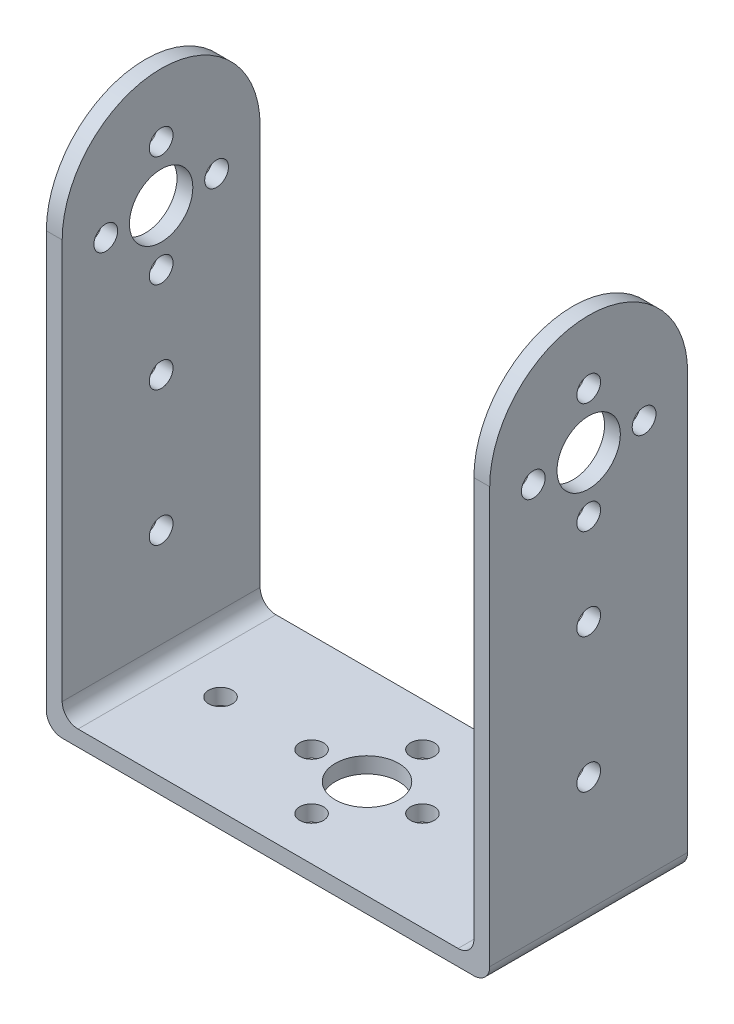
SolidWorks part; units mm, degrees
ref_plane "Front Plane" through (0, 0, 0) normal (0, 0, 1) x (1, 0, 0)
ref_plane "Top Plane" through (0, 0, 0) normal (0, 1, 0) x (1, 0, 0)
ref_plane "Right Plane" through (0, 0, 0) normal (1, 0, 0) x (0, 0, -1)
sketch "Sketch1" plane through (0, 0, 0) normal (0, 1, 0) x (1, 0, 0)
  line L0 (-26, 12.5) -> (-28, 12.5)
  line L2 (-26, -12.5) -> (-26, 12.5)
  line L4 (26, -12.5) -> (26, 12.5)
  line L5 (-26, -12.5) -> (-28, -12.5)
  line L6 (-26, 12.5) -> (26, 12.5)
  line L7 (28, -12.5) -> (26, -12.5)
  line L8 (28, -12.5) -> (28, 12.5)
  line L9 (28, 12.5) -> (26, 12.5)
  line L10 (-28, -12.5) -> (-28, 12.5)
  line L11 (-26, -12.5) -> (26, -12.5)
  line L12 (-26, 12.5) -> (26, -12.5) construction
  line L13 (26, 12.5) -> (-26, -12.5) construction
  point P0 (0, 0)
  point P6 (0, 0)
  point P11 (0, 0)
  dimension "D1" = 2
  dimension "D2" = 2
  dimension "D3" = 25
  dimension "D4" = 52
extrude "Boss-Extrude1" add sketch "Sketch1" against normal blind 2 contours L2 L11 L4 L6 | L10 L5 L2 L0 | L8 L9 L4 L7 region at (-27, 0, 0) region at (0, 0, 0) region at (27, 0, 0)
extrude "Boss-Extrude2" add sketch "Sketch1<3>" along normal blind 65 contours L10 L5 L2 L0 | L8 L9 L4 L7 region at (-27, 0, 0) region at (27, 0, 0)
sketch "Sketch1<3>" plane through (0, 0, 0) normal (0, 1, 0) x (1, 0, 0) same geometry as "Sketch1"
fillet "Fillet4" radius 2 4 edges at (28, -2, 0) (26, 0, 0) (-28, -2, 0) (-26, 0, 0)
sketch "Sketch2" plane through (28, 0, 0) normal (1, 0, 0) x (0, 0, -1)
  line L0 (-12.5, 0) -> (-12.5, 65) construction
  line L1 (12.5, 0) -> (12.5, 65) construction
  line L2 (-12.5, 65) -> (12.5, 65) construction
  line L4 (-12.5, 52.5) -> (-12.5, 65)
  line L5 (-12.5, 65) -> (0, 65)
  line L6 (0, 65) -> (12.5, 65)
  line L7 (12.5, 65) -> (12.5, 52.5)
  line L8 (0, -2) -> (0, 14.5) construction
  line L9 (12.5, -2) -> (-12.5, -2) construction
  line L10 (0, 14.5) -> (0, 31.5) construction
  line L11 (0, 31.5) -> (0, 50) construction
  arc A0 (12.5, 52.5) -> (-12.5, 52.5) centre (0, 52.5) ccw
  circle A1 centre (0, 14.5) radius 1.5
  circle A2 centre (0, 31.5) radius 1.5
  circle A3 centre (0, 50) radius 4
  circle A4 centre (0, 50) radius 7 construction
  circle A5 centre (0, 57) radius 1.5
  circle A6 centre (7, 50) radius 1.5
  circle A7 centre (0, 43) radius 1.5
  circle A8 centre (-7, 50) radius 1.5
  line M2 (-12.5, 65) -> (-12.5, 0)
  line M4 (12.5, 0) -> (12.5, 65)
  line M5 (12.5, 65) -> (-12.5, 65)
  dimension "D1" = 4
extrude "Cut-Extrude1" cut sketch "Sketch2" against normal blind 65 contours A0 M5 M2 | A0 M4 M5 | A2 | A1 | A3 | A8 | A5 | A6 | A7 region at (28, 62.2079, -9.7079) region at (28, 62.2079, 9.7079) region at (28, 14.5, 0) region at (28, 31.5, 0)
sketch "Sketch3" plane through (0, 0, 0) normal (0, 1, 0) x (1, 0, 0)
  line L0 (0, 0) -> (-18.5, 0) construction
  line L1 (0, 0) -> (18.5, 0) construction
  circle A0 centre (0, 0) radius 4
  circle A1 centre (0, 0) radius 7 construction
  circle A2 centre (0, 7) radius 1.5
  circle A3 centre (7, 0) radius 1.5
  circle A4 centre (0, -7) radius 1.5
  circle A5 centre (-7, 0) radius 1.5
  circle A6 centre (-18.5, 0) radius 1.5
  circle A7 centre (18.5, 0) radius 1.5
  dimension "D1" = 4
extrude "Cut-Extrude2" cut sketch "Sketch3" against normal blind 65
